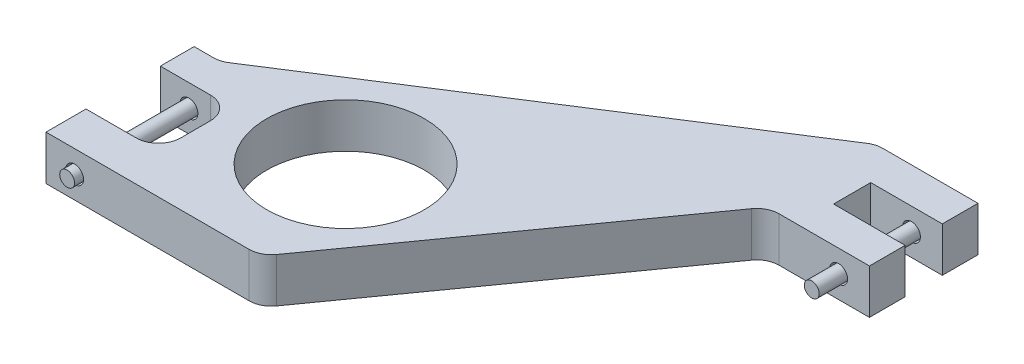
SolidWorks part; units mm, degrees
ref_plane "Front Plane" through (0, 0, 0) normal (0, 0, 1) x (1, 0, 0)
ref_plane "Top Plane" through (0, 0, 0) normal (0, 1, 0) x (1, 0, 0)
ref_plane "Right Plane" through (0, 0, 0) normal (1, 0, 0) x (0, 0, -1)
sketch "Sketch21" plane through (0, 0, 0) normal (0, 1, 0) x (1, 0, 0)
  line L0 (-88.2958, -45.3118) -> (-79.7279, -45.3118)
  line L1 (-75.9179, -49.1218) -> (-75.9179, -54.2018)
  line L2 (-79.7279, -58.0118) -> (-88.2958, -58.0118)
  line L3 (-88.2958, -64.8542) -> (-88.2958, -58.0118)
  line L4 (-73.302, -29.635) -> (-70.5137, -29.635)
  line L5 (-70.5137, -29.635) -> (-70.5137, -64.8542) construction
  line L6 (-70.5137, -64.8542) -> (-88.2958, -64.8542)
  line L7 (-83.3988, 63.5008) -> (4.1804, 63.5008) construction
  line L8 (52.8639, 77.8829) -> (52.8639, -77.8829) construction
  line L9 (1.9027, -14.2886) -> (1.9027, -8.1861)
  line L10 (1.9027, 4.2664) -> (-14.3984, 4.2664)
  line L11 (-10.3341, -8.1861) -> (1.9027, -8.1861)
  line L12 (-10.3341, -1.8361) -> (-10.3341, -8.1861)
  line L13 (1.9027, -1.8361) -> (-10.3341, -1.8361)
  line L14 (1.9027, -1.8361) -> (1.9027, 4.2664)
  line L15 (-12.4522, 12.9339) -> (21.2265, 12.9339) construction
  line L16 (1.9027, -14.2886) -> (-13.5525, -14.2886)
  line L17 (-15.5143, -14.2886) -> (-15.5143, 4.2664) construction
  line L18 (-137.175, 18.8036) -> (-137.175, 26.8947) construction
  line L19 (-88.2958, -45.3118) -> (-88.2958, -39.5337)
  line L20 (-82.9324, -38.9317) -> (-16.4539, 3.6644)
  line L21 (-16.6539, -15.8855) -> (-50.4581, -63.2573)
  line L22 (-70.5137, -64.8542) -> (-53.5594, -64.8542)
  line L23 (-84.9879, -39.5337) -> (-88.2958, -39.5337)
  circle A0 centre (-57.944, -43.9974) radius 13.4824
  circle A1 centre (-57.944, -43.9974) radius 21.0273 construction
  arc A2 (-14.3984, 4.2664) -> (-16.4539, 3.6644) centre (-14.3984, 0.4564) ccw
  arc A3 (-13.5525, -14.2886) -> (-16.6539, -15.8855) centre (-13.5525, -18.0986) ccw
  arc A4 (-50.4581, -63.2573) -> (-53.5594, -64.8542) centre (-53.5594, -61.0442) cw
  arc A5 (-82.9324, -38.9317) -> (-84.9879, -39.5337) centre (-84.9879, -35.7237) cw
  arc A6 (-75.9179, -54.2018) -> (-79.7279, -58.0118) centre (-79.7279, -54.2018) cw
  arc A7 (-79.7279, -45.3118) -> (-75.9179, -49.1218) centre (-79.7279, -49.1218) cw
  point P42 (-75.9179, -58.0118)
  point P45 (-75.9179, -45.3118)
  dimension "D3" = 3.81
  dimension "D1" = 87.5792
  dimension "D2" = 6.35
  dimension "D4" = 18.555
  dimension "D7" = 12.7
extrude "Extrude1" add sketch "Sketch21" along normal mid plane 7.62 contours L20 L23 L19 L0 L1 L2 L3 L6 L22 L21 L16 L9 L11 L12 L13 L14 L10 A0
sketch "Sketch22" plane through (-0.8004, 0, 0) normal (0, 0, -1) x (-1, 0, 0)
  line L0 (-2.7031, 0) -> (93.1169, 0) construction
  circle A0 centre (2.563, 0) radius 1.524
  circle A1 centre (82.5984, 0) radius 1.524
  dimension "D1" = 80.0354
  dimension "D2" = 3.048
extrude "Extrude2" cut sketch "Sketch22" along normal mid plane 129.7432
sketch "Sketch23" plane through (0, 0, 0) normal (0, 0, 1) x (1, 0, 0)
  circle A0 centre (-83.3988, 0) radius 1.27
  circle A1 centre (-3.3634, 0) radius 1.27
  dimension "D1" = 2.54
extrude "Extrude3" add sketch "Sketch23" along normal blind 30.574 from offset 35.56 separate body contours A0
extrude "Extrude4" add sketch "Sketch23<3>" along normal blind 23.97 from offset 5.08 separate body contours A1 offset against normal yes
sketch "Sketch23<3>" plane through (0, 0, 0) normal (0, 0, 1) x (1, 0, 0) same geometry as "Sketch23"
